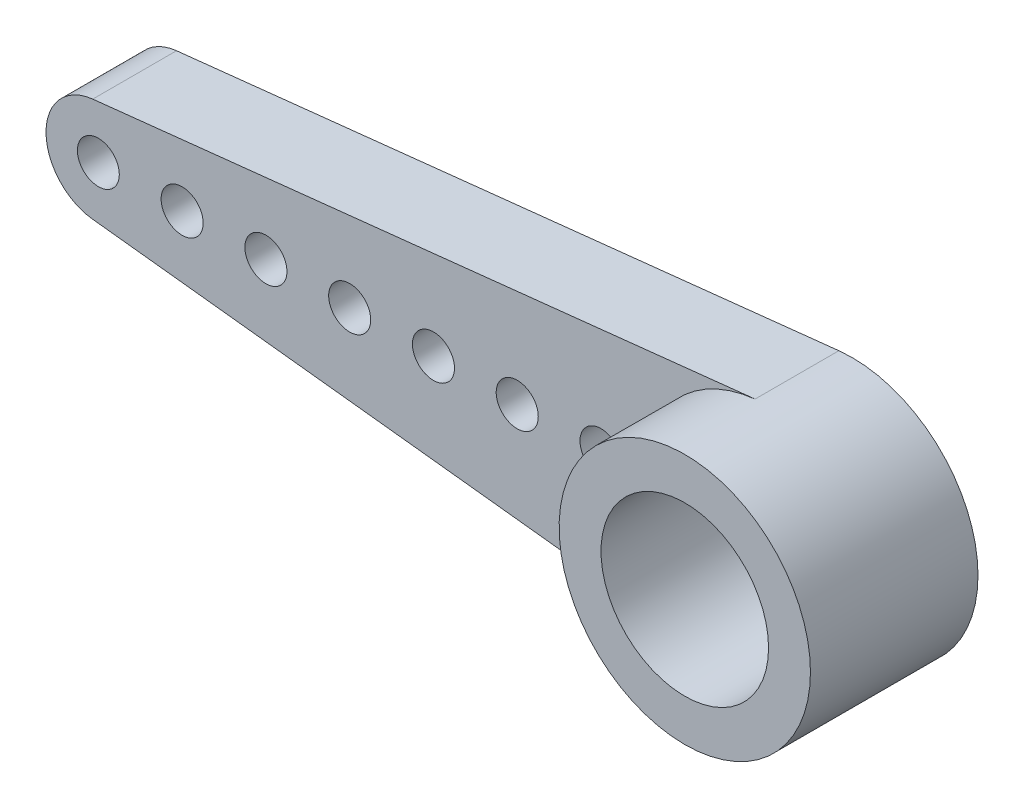
SolidWorks part; units mm, degrees
ref_plane "前视基准面" through (0, 0, 0) normal (0, 0, 1) x (1, 0, 0)
ref_plane "上视基准面" through (0, 0, 0) normal (0, 1, 0) x (1, 0, 0)
ref_plane "右视基准面" through (0, 0, 0) normal (1, 0, 0) x (0, 0, -1)
sketch "草图1" plane through (0, 0, 0) normal (0, 0, 1) x (1, 0, 0)
  line L1 (-16.1395, -1.2066) -> (-0.3348, -2.9813)
  line L2 (-16.134, 1.2784) -> (-0.3215, 2.9827)
  circle A0 centre (0, 0) radius 3
  circle A1 centre (0, 0) radius 2
  arc A2 (-16.134, 1.2784) -> (-16.1395, -1.2066) centre (-16, 0.0356) ccw
  circle A3 centre (-16, 0.0356) radius 0.5
  dimension "D1" = 6
  dimension "D3" = 2.5
  dimension "D5" = 1.25
  dimension "D9" = 1
  dimension "D4" = 16
  dimension "D6" = 3
  dimension "D7" = 1.25
  dimension "D8" = 3
  dimension "D2" = 1
extrude "凸台-拉伸1" add sketch "草图1" along normal blind 4 contours A0 A1 region at (-2.9151, 0.0065, 0)
extrude "凸台-拉伸2" add sketch "草图1<3>" along normal blind 2 contours L2 A2 L1 A0 A3 region at (-8.6198, 0.0192, 0)
sketch "草图1<3>" plane through (0, 0, 0) normal (0, 0, 1) x (1, 0, 0) same geometry as "草图1"
sketch "草图2" plane through (0, 0, 2) normal (0, 0, 1) x (1, 0, 0)
  line L0 (-16, 0.0356) -> (49983.8763, -111.1624) construction
  circle A0 centre (-14, 0.0311) radius 0.5021
  circle A1 centre (-16, 0.0356) radius 0.5 construction
  circle A2 centre (-12, 0.0311) radius 0.5021
  circle A3 centre (-10, 0.0311) radius 0.5021
  circle A4 centre (-8, 0.0311) radius 0.5021
  circle A5 centre (-6, 0.0311) radius 0.5021
  circle A6 centre (-4, 0.0311) radius 0.5021
  dimension "D1" = 1.0042
  dimension "D2" = 2
  dimension "D3" = 6
extrude "切除-拉伸1" cut sketch "草图2" against normal through all
